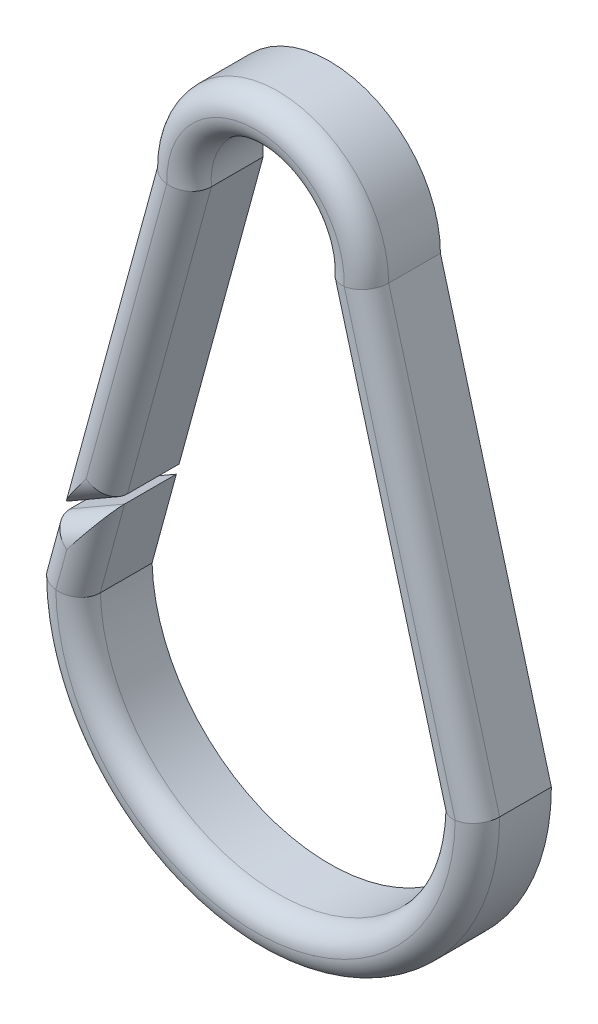
SolidWorks part; units mm, degrees
ref_plane "Спереди" through (0, 0, 0) normal (0, 0, 1) x (1, 0, 0)
ref_plane "Сверху" through (0, 0, 0) normal (0, 1, 0) x (1, 0, 0)
ref_plane "Справа" through (0, 0, 0) normal (1, 0, 0) x (0, 0, -1)
sketch "Эскиз1" plane through (0, 0, 0) normal (0, 0, 1) x (1, 0, 0)
  line L0 (0, 0) -> (0, 22.5) construction
  line L1 (-7.5, 22.5) -> (-15, -5)
  line L2 (0, 0) -> (0, -5) construction
  line L3 (0, 22.5) -> (0, 43.7896) construction
  line L4 (0, -5) -> (0, -28.6222) construction
  line L5 (7.5, 22.5) -> (15, -5)
  line L6 (-4.4863, 22.1486) -> (-11.994, -5.3797)
  line L7 (4.4863, 22.1486) -> (11.994, -5.3797)
  arc A0 (7.5, 22.5) -> (-7.5, 22.5) centre (0, 22.5) ccw
  arc A1 (-15, -5) -> (15, -5) centre (0, -5) ccw
  arc A2 (-11.994, -5.3797) -> (11.994, -5.3797) centre (0, -5) ccw
  arc A3 (4.4863, 22.1486) -> (-4.4863, 22.1486) centre (0, 22.5) ccw
  dimension "D1" = 30
  dimension "D2" = 15
  dimension "D3" = 50
  dimension "D4" = 5
  dimension "D5" = 3
extrude "Бобышка-Вытянуть1" add sketch "Эскиз1" along normal blind 5
sketch "Эскиз2" plane through (0, 0, 0) normal (0, 0, 1) x (1, 0, 0)
  line L0 (0, 0) -> (-21.2469, 0) construction
  line L1 (-8.25, 2.433) -> (-16.9103, -2.567)
  line L2 (-8, 2) -> (-16.6603, -3)
  line L3 (-8.25, 2.433) -> (-8, 2)
  line L4 (-16.9103, -2.567) -> (-16.6603, -3)
  dimension "D2" = 30
  dimension "D3" = 10
  dimension "D4" = 8
  dimension "D5" = 2
  dimension "D1" = 0.5
extrude "Вырез-Вытянуть2" cut sketch "Эскиз2" along normal through all
fillet "Скругление2" radius 1.5 12 edges at (0, 30, 5) (11.25, 8.75, 5) (0, -20, 5) (-14.5212, -3.2443, 5) (-12.197, -0.4231, 5) (-11.1728, -2.3687, 5) (0, -17, 5) (8.2401, 8.3845, 5) (0, 27, 5) (-7.3255, 11.7381, 5) (-12.0101, 0.2621, 5) (-10.6777, 10.8484, 5)
scale "Масштаб1" scale about centroid uniform scaling yes scale factor 0.5
